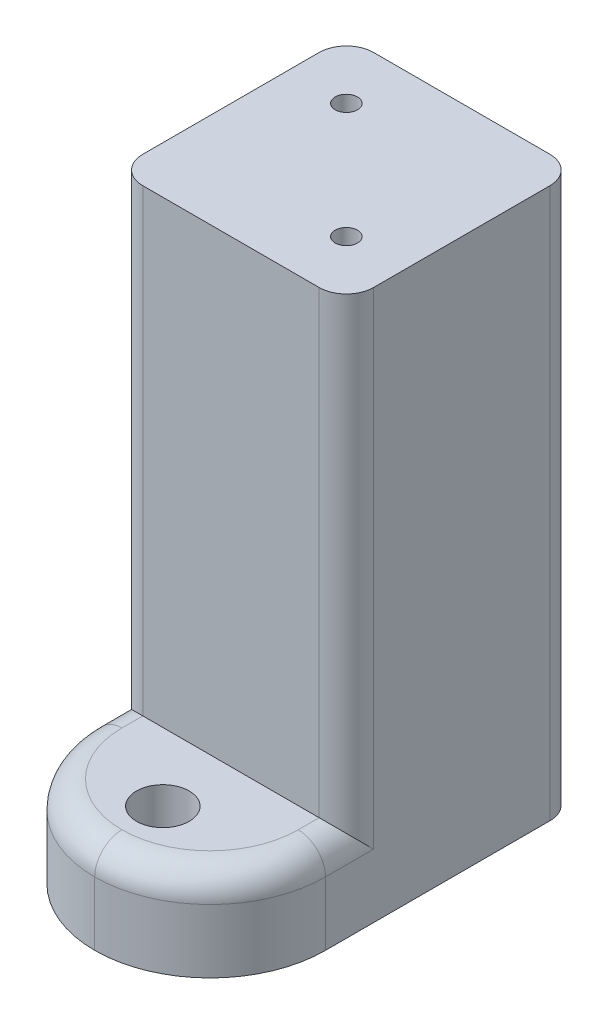
SolidWorks part; units mm, degrees
ref_plane "Front" through (0, 0, 0) normal (0, 0, 1) x (1, 0, 0)
ref_plane "Top" through (0, 0, 0) normal (0, 1, 0) x (1, 0, 0)
ref_plane "Right" through (0, 0, 0) normal (1, 0, 0) x (0, 0, -1)
sketch "Sketch1" plane through (0, 0, 0) normal (0, 1, 0) x (1, 0, 0)
  line L1 (-12.7, 40.4) -> (12.7, 40.4)
  line L2 (-12.7, 40.4) -> (-12.7, 0)
  line L3 (-12.7, 0) -> (12.7, 0)
  line L4 (12.7, 40.4) -> (12.7, 0)
  dimension "D1" = 25.4
  dimension "D2" = 40.4
extrude "Boss-Extrude1" add sketch "Sketch1" along normal blind 10
sketch "Sketch2" plane through (0, 10, 0) normal (0, 1, 0) x (1, 0, 0)
  line L0 (12.7, 0) -> (12.7, 40.4) construction
  line L1 (-12.7, 40.4) -> (12.7, 40.4)
  line L2 (-12.7, 40.4) -> (-12.7, 15)
  line L3 (-12.7, 15) -> (12.7, 15)
  line L4 (12.7, 40.4) -> (12.7, 15)
  dimension "D1" = 25.4
extrude "Boss-Extrude2" add sketch "Sketch2" along normal blind 50.54
sketch "Sketch3" plane through (0, 60.54, 0) normal (0, 1, 0) x (1, 0, 0)
  line L0 (12.7, 40.4) -> (-12.7, 40.4) construction
  line L1 (-12.7, 40.4) -> (-12.7, 15) construction
  circle A0 centre (-6.35, 34.05) radius 1.2303
  circle A1 centre (6.35, 21.35) radius 1.2303
  dimension "D1" = 12.7
  dimension "D2" = 12.7
  dimension "D3" = 6.35
  dimension "D4" = 2.4606
  dimension "D5" = 6.35
extrude "Cut-Extrude1" cut sketch "Sketch3" against normal blind 20
sketch "Sketch4" plane through (0, 10, 0) normal (0, 1, 0) x (1, 0, 0)
  line L0 (-12.7, 15) -> (12.7, 0) construction
  circle A0 centre (0, 7.5) radius 2.9
  dimension "D1" = 5.8
extrude "Cut-Extrude2" cut sketch "Sketch4" against normal through all
fillet "Fillet1" radius 3 7 edges at (-12.7, 10, -7.5) (12.7, 10, -7.5) (0, 10, 0) (-12.7, 30.27, -40.4) (12.7, 30.27, -40.4) (12.7, 35.27, -15) (-12.7, 35.27, -15)
fillet "Fillet2" radius 12.7 4 edges at (-11.8213, 9.1213, -0.8787) (11.8213, 9.1213, -0.8787) (12.7, 3.5, 0) (-12.7, 3.5, 0)
